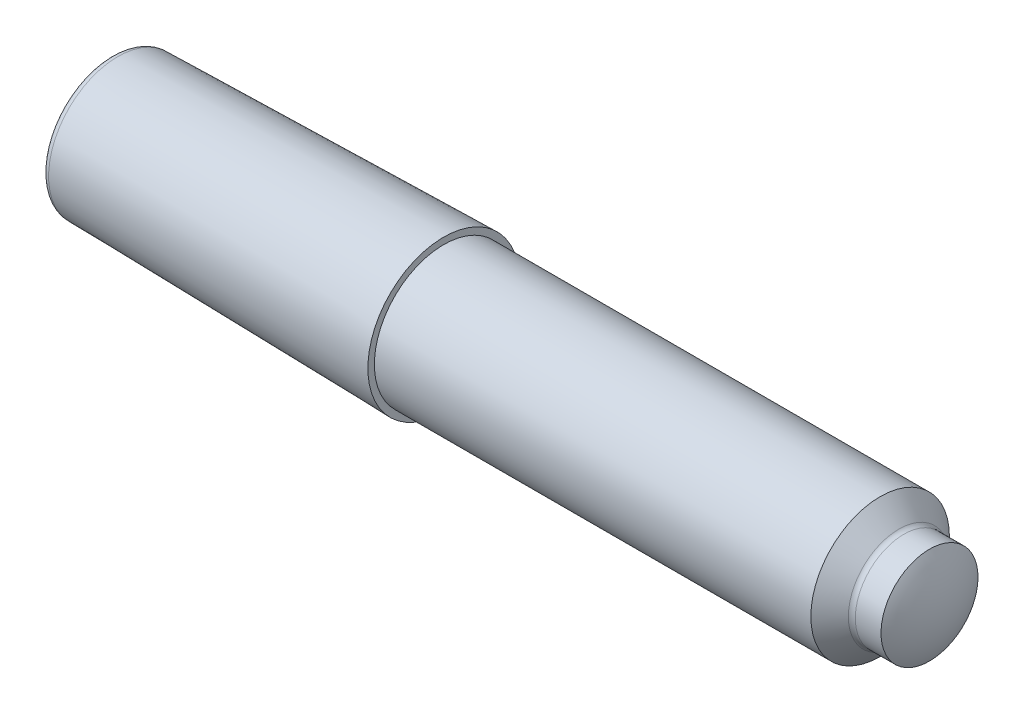
SolidWorks part; units mm, degrees
ref_plane "Front" through (0, 0, 0) normal (0, 0, 1) x (1, 0, 0)
ref_plane "Top" through (0, 0, 0) normal (0, 1, 0) x (1, 0, 0)
ref_plane "Right" through (0, 0, 0) normal (1, 0, 0) x (0, 0, -1)
sketch "Sketch1" plane through (0, 0, 0) normal (0, 0, 1) x (1, 0, 0)
  line L0 (0, 0) -> (0, 2.25)
  line L1 (0.245, 2.5) -> (12, 2.7351)
  line L2 (0, 2.4951) -> (12, 2.4951) construction
  line L3 (14.4, 2.5) -> (27.75, 2.5)
  line L4 (27.75, 2.5) -> (28.5, 1.75)
  line L5 (28.5, 1.75) -> (29.5311, 1.75)
  line L6 (0, 0) -> (-2.8036, 0) construction
  line L7 (0, 0) -> (30, 0)
  line L8 (14.4, 2.5) -> (12, 2.5)
  line L9 (12, 2.5) -> (12, 2.7351)
  line L10 (12, 2.7351) -> (12, 2.4951) construction
  arc A0 (30, 0) -> (29.5311, 1.75) centre (26.5, 0) ccw
  arc A1 (0, 2.25) -> (0.245, 2.5) centre (0.25, 2.25) cw
  dimension "D6" = 1.5
  dimension "D8" = 45
  dimension "b" = 15.6
  dimension "d1" = 5
  dimension "D4" = 0.24
revolve "Body" add sketch "Sketch1" angle 360 about L6
cosmetic thread "ThreadCosmetic1" [suppressed] parameters "b"=13.35, "d"=4
fillet "Fillet1" radius 0.25 1 edges at (28.5, 0, -1.75)
sketch "Sketch2" plane through (0, 0, 0) normal (0, 0, 1) x (1, 0, 0)
  line L0 (27.5, 3) -> (28, 3)
  line L1 (28, 3) -> (28, 2.5)
  line L2 (28, 2.5) -> (27.75, 2.067)
  line L3 (27.75, 2.067) -> (27.5, 2.5)
  line L4 (27.5, 2.5) -> (27.5, 3)
  line L5 (0, 0) -> (44.52, 0) construction
  line L6 (27.75, 2.5) -> (12, 2.5) construction
  line L11 (27.75, 2.5) -> (27.75, -2.5) construction
  dimension "D1" = 0.5
revolve "Cut-Revolve10" [suppressed] cut sketch "Sketch2" angle 360 about L5
pattern_linear "LPattern10" [suppressed] count 22 spacing 0.6 along (-1, 0, 0) of bodies 102
equation "\"r@Sketch1\" =  \"d3@Sketch1\""
equation "\"D4@Sketch1\" = (  \"l@Sketch1\" - \"b@Sketch1\" - \"a@Sketch1\" )  / 50"
equation "\"D11@Sketch1\" = \"d1@Sketch1\" / 20"
equation "\"D1@Fillet1\" = \"D11@Sketch1\""
equation "\"b@ThreadCosmetic1\" = \"b@Sketch1\" - \"D6@Sketch1\" - (  (  \"d2@Sketch1\" - \"d3@Sketch1\" )  / 2 ) "
equation "\"D3@LPattern10\" =\"D1@Sketch2\" * 1.2"
equation "\"D1@LPattern10\" =\"b@ThreadCosmetic1\" / \"D3@LPattern10\""
equation "\"d@ThreadCosmetic1\" = \"d2@Sketch1\" * 4 / 5"
equation "\"D1@Sketch2\" = (  \"d2@Sketch1\" - \"d@ThreadCosmetic1\" )  / 2"
